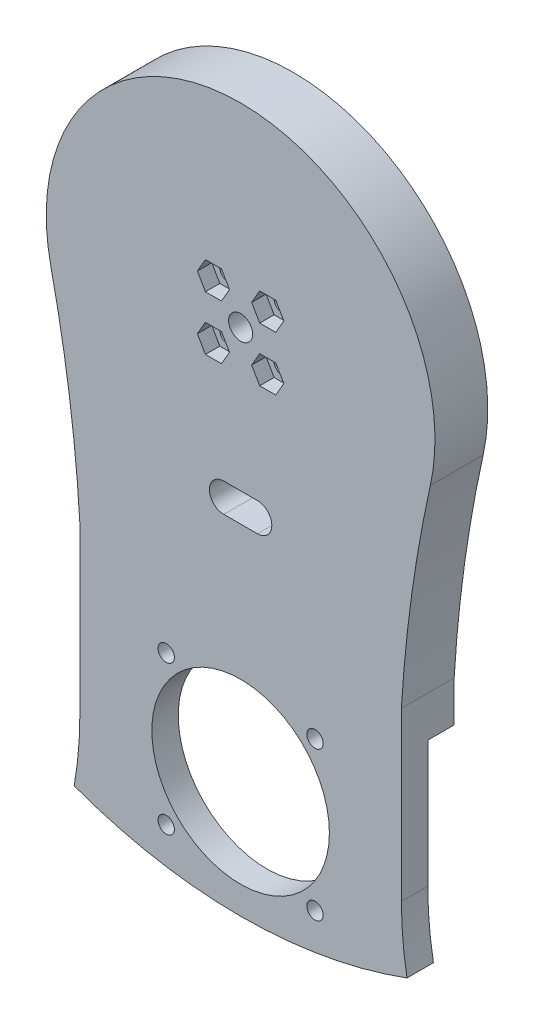
SolidWorks part; units mm, degrees
ref_plane "Front Plane" through (0, 0, 0) normal (0, 0, 1) x (1, 0, 0)
ref_plane "Top Plane" through (0, 0, 0) normal (0, 1, 0) x (1, 0, 0)
ref_plane "Right Plane" through (0, 0, 0) normal (1, 0, 0) x (0, 0, -1)
sketch "Sketch1" plane through (0, 0, 0) normal (0, 0, 1) x (1, 0, 0)
  line L0 (-79.9282, -98) -> (79.9282, -98) construction
  line L1 (-21.5, 21.5) -> (21.5, 21.5)
  line L2 (-21.5, 21.5) -> (-21.5, -21.5)
  line L3 (-21.5, -21.5) -> (21.5, -21.5)
  line L4 (21.5, 21.5) -> (21.5, -21.5)
  line L5 (-21.5, 21.5) -> (21.5, -21.5) construction
  line L6 (-21.5, -21.5) -> (21.5, 21.5) construction
  line L7 (-33.5, 21.5) -> (33.5, 21.5)
  line L8 (-33.5, 21.5) -> (-33.5, -31.5)
  line L9 (-33.5, -31.5) -> (33.5, -31.5)
  line L10 (33.5, 21.5) -> (33.5, -31.5)
  line L11 (-33.5, 21.5) -> (33.5, -31.5) construction
  line L12 (-33.5, -31.5) -> (33.5, 21.5) construction
  line L13 (-59.5091, 0) -> (49.588, 0) construction
  line L14 (0, -98) -> (-73.46, -24.54) construction
  line L15 (0, -98) -> (0, 0) construction
  line L16 (0, -98) -> (73.46, -24.54) construction
  line L17 (-51.5944, -53.7053) -> (51.5944, -53.7053)
  line L18 (0, -98) -> (0, 62) construction
  line L19 (0, 62) -> (0, 86) construction
  line L20 (-33.5, -31.5) -> (-38.3942, -31.5)
  line L21 (33.5, -31.5) -> (38.3942, -31.5)
  line L22 (-33.5, -30) -> (33.5, -30)
  line L23 (33.5, -30) -> (37.8422, -30)
  line L24 (-33.5, -30) -> (-37.8422, -30)
  circle A2 centre (-33.5, 0) radius 2.5982 construction
  circle A3 centre (-48.0833, -49.9167) radius 10.7942 construction
  circle A4 centre (48.0833, -49.9167) radius 10.7942 construction
  circle A5 centre (33.5, 0) radius 2.5982 construction
  arc A6 (-51.5944, -53.7053) -> (-33.5, -4.8509) centre (-108.5, -4.8509) ccw
  circle A7 centre (0, -98) radius 34.0704
  circle A8 centre (0, -98) radius 68
  arc A9 (51.5944, -53.7053) -> (33.5, -4.8509) centre (108.5, -4.8509) cw
  circle A10 centre (0, 0) radius 18.5
  point P0 (0, 0)
  point P6 (0, -5)
  point P38 (0, -98)
  dimension "D6" = 136
  dimension "D7" = 68.1408
  dimension "D10" = 75
  dimension "D11" = 75
  dimension "D13" = 37
  dimension "D1" = 43
  dimension "D2" = 43
  dimension "D3" = 53
  dimension "D4" = 10
  dimension "D5" = 12
  dimension "D8" = 26.3509
  dimension "D9" = 26.3509
  dimension "D12" = 103.1888
  dimension "D14" = 18.4167
  dimension "D15" = 14.5833
  dimension "D16" = 14.5833
  dimension "D17" = 18.4167
  dimension "D18" = 22.2053
  dimension "D19" = 159.8564
  dimension "D20" = 103.8881
  dimension "D21" = 103.8881
  dimension "D22" = 160
  dimension "D23" = 62
  dimension "D24" = 184
extrude "Boss-Extrude1" add sketch "Sketch1" along normal blind 5.5 contours A6 L24 L8 | L8 L22 L10 L7 L4 L3 L2 | L23 A9 L10 | L4 L1 L2 L3 A10 | A8 A9 L21 L9 | A8 L9 L20 A6 | A8 L22 L8 L9 | A8 L9 L10 L22 | L21 A9 L23 L10 | A6 L20 L8 L24 region at (0, 20.8919, 0) region at (-22.3451, 0, 0) region at (-34.7959, -23.7497, 0) region at (34.7959, -23.7497, 0) region at (-21.2623, -30.6909, 0) region at (-35.8103, -30.7649, 0) region at (35.8103, -30.7649, 0) region at (21.2623, -30.6909, 0) region at (-34.2049, -36.6082, 0) region at (34.2049, -36.6082, 0)
sketch "Sketch2" plane through (0, 0, 5.5) normal (0, 0, 1) x (1, 0, 0)
  line L0 (0, 0) -> (0, 82) construction
  line L1 (-33.5, 21.5) -> (33.5, 21.5)
  line L2 (33.5, 21.5) -> (33.5, 30)
  line L3 (33.5, 30) -> (-33.5, 30)
  line L4 (-33.5, 21.5) -> (-33.5, 30)
  line L5 (-8, 82) -> (8, 82) construction
  line L6 (-5.6569, 87.6569) -> (0, 82)
  line L7 (-5.6569, 76.3431) -> (0, 82) construction
  line L8 (0, 82) -> (5.6569, 87.6569) construction
  line L9 (0, 82) -> (5.6569, 76.3431) construction
  circle A0 centre (0, 0) radius 18.5 construction
  circle A1 centre (0, -98) radius 68 construction
  circle A2 centre (0, 82) radius 2.5
  circle A3 centre (0, 82) radius 8 construction
  circle A4 centre (0, 82) radius 40.5
  circle A5 centre (0, 0) radius 27.5 construction
  arc A6 (-33.5, 30) -> (-39.5426, 73.2458) centre (-309.506, 13.4799) ccw
  circle A7 centre (0, 82) radius 40 construction
  arc A8 (33.5, 30) -> (39.5426, 73.2458) centre (309.506, 13.4799) cw
  circle A14 centre (-5.6569, 87.6569) radius 1.7
  circle A15 centre (5.6569, 87.6569) radius 1.7
  circle A16 centre (5.6569, 76.3431) radius 1.7
  circle A17 centre (-5.6569, 76.3431) radius 1.7
  line M4 (33.5, 21.5) -> (-33.5, 21.5)
  dimension "D3" = 136
  dimension "D4" = 37
  dimension "D5" = 5
  dimension "D6" = 16
  dimension "D7" = 81
  dimension "D8" = 55
  dimension "D9" = 30
  dimension "D10" = 80
  dimension "D11" = 553
  dimension "D12" = 276.5
  dimension "D13" = 45
  dimension "D14" = 3.4
  dimension "D15" = 3.4
  dimension "D16" = 3.4
  dimension "D17" = 3.4
  dimension "D1" = 98
  dimension "D2" = 180
  dimension "D18" = 45
  dimension "D19" = 45
  dimension "D20" = 45
extrude "Boss-Extrude2" add sketch "Sketch2" against normal blind 11 contours L3 A8 A4 A6 | L4 L2 L3 M4 | A4 A2 region at (0, 25.75, 5.5) region at (0, 40.4579, 5.5) region at (-4.2786, 121.1212, 5.5)
sketch "Sketch3" plane through (0, 0, 5.5) normal (0, 0, 1) x (1, 0, 0)
  line L1 (-15.5, -15.5) -> (15.5, -15.5) construction
  line L2 (-15.5, -15.5) -> (-15.5, 15.5) construction
  line L3 (-15.5, 15.5) -> (15.5, 15.5) construction
  line L4 (15.5, -15.5) -> (15.5, 15.5) construction
  line L5 (-15.5, -15.5) -> (15.5, 15.5) construction
  line L6 (-15.5, 15.5) -> (15.5, -15.5) construction
  circle A0 centre (-15.5, 15.5) radius 1.7
  circle A1 centre (15.5, 15.5) radius 1.7
  circle A2 centre (15.5, -15.5) radius 1.7
  circle A3 centre (-15.5, -15.5) radius 1.7
  point P0 (0, 0)
  point P16 (0, 0)
  dimension "D3" = 3.4
  dimension "D1" = 31
  dimension "D2" = 31
  dimension "D4" = 4
extrude "Cut-Extrude1" cut sketch "Sketch3" against normal through all contours A3 | A2 | A1 | A0
sketch "Sketch4" plane through (0, 0, 0) normal (0, 0, -1) x (-1, 0, 0)
  line L0 (-33.5, 21.5) -> (33.5, 21.5) construction
  line L1 (-33.5, 21.5) -> (-33.5, -18.5) construction
  line L2 (33.5, 21.5) -> (33.5, -18.5) construction
  line L3 (-33.5, -18.5) -> (33.5, -18.5) construction
  line L4 (-33.5, -18.5) -> (33.5, -18.5)
  line L5 (-65, -0.2716) -> (-65, -64.2716)
  line L6 (-65, -64.2716) -> (65, -64.2716)
  line L7 (65, -0.2716) -> (65, -64.2716)
  circle A0 centre (0, 0) radius 18.5
  arc A1 (-65, -0.2716) -> (65, -0.2716) centre (0, 75.7218) ccw
  arc M14 (51.5944, -53.7053) -> (33.5, -4.8509) centre (108.5, -4.8509) cw
  arc M18 (-33.5, -4.8509) -> (-51.5944, -53.7053) centre (-108.5, -4.8509) cw
  arc M19 (-51.5944, -53.7053) -> (51.5944, -53.7053) centre (0, -98) cw
  dimension "D2" = 200
  dimension "D3" = 100
  dimension "D6" = 37
  dimension "D1" = 40
  dimension "D4" = 64
  dimension "D5" = 130
  dimension "D7" = 64
extrude "Cut-Extrude11" cut sketch "Sketch4" against normal blind 10 contours A1 M18 M19 M14 region at (0, -29.6272, 0)
sketch "Sketch5" plane through (0, 0, 5.5) normal (0, 0, 1) x (1, 0, 0)
  line L0 (-7.3319, 90.558) -> (-3.9819, 84.7557) construction
  line L1 (-7.3319, 84.7557) -> (-3.9819, 90.558) construction
  line L2 (-9.0069, 87.6569) -> (-2.3069, 87.6569) construction
  line L3 (2.3069, 87.6569) -> (9.0069, 87.6569) construction
  line L4 (-9.0069, 76.3431) -> (-2.3069, 76.3431) construction
  line L5 (2.3069, 76.3431) -> (9.0069, 76.3431) construction
  line L6 (3.9819, 90.558) -> (7.3319, 84.7557) construction
  line L7 (3.9819, 84.7557) -> (7.3319, 90.558) construction
  line L8 (3.9819, 79.2443) -> (7.3319, 73.442) construction
  line L9 (3.9819, 73.442) -> (7.3319, 79.2443) construction
  line L10 (-7.3319, 79.2443) -> (-3.9819, 73.442) construction
  line L11 (-7.3319, 73.442) -> (-3.9819, 79.2443) construction
  line L12 (-7.3319, 90.558) -> (-3.9819, 90.558)
  line L13 (-3.9819, 90.558) -> (-2.3069, 87.6569)
  line L14 (-2.3069, 87.6569) -> (-3.9819, 84.7557)
  line L15 (-3.9819, 84.7557) -> (-7.3319, 84.7557)
  line L16 (-7.3319, 84.7557) -> (-9.0069, 87.6569)
  line L17 (-9.0069, 87.6569) -> (-7.3319, 90.558)
  line L18 (3.9819, 90.558) -> (7.3319, 90.558)
  line L19 (7.3319, 90.558) -> (9.0069, 87.6569)
  line L20 (9.0069, 87.6569) -> (7.3319, 84.7557)
  line L21 (7.3319, 84.7557) -> (3.9819, 84.7557)
  line L22 (3.9819, 84.7557) -> (2.3069, 87.6569)
  line L23 (2.3069, 87.6569) -> (3.9819, 90.558)
  line L24 (-7.3319, 79.2443) -> (-9.0069, 76.3431)
  line L25 (-9.0069, 76.3431) -> (-7.3319, 73.442)
  line L26 (-7.3319, 73.442) -> (-3.9819, 73.442)
  line L27 (-3.9819, 73.442) -> (-2.3069, 76.3431)
  line L28 (-2.3069, 76.3431) -> (-3.9819, 79.2443)
  line L29 (-3.9819, 79.2443) -> (-7.3319, 79.2443)
  line L30 (3.9819, 79.2443) -> (7.3319, 79.2443)
  line L31 (7.3319, 79.2443) -> (9.0069, 76.3431)
  line L32 (9.0069, 76.3431) -> (7.3319, 73.442)
  line L33 (7.3319, 73.442) -> (3.9819, 73.442)
  line L34 (3.9819, 73.442) -> (2.3069, 76.3431)
  line L35 (2.3069, 76.3431) -> (3.9819, 79.2443)
  circle A0 centre (-5.6569, 87.6569) radius 3.35 construction
  circle A1 centre (5.6569, 87.6569) radius 3.35 construction
  circle A2 centre (5.6569, 76.3431) radius 3.35 construction
  circle A3 centre (-5.6569, 76.3431) radius 3.35 construction
  dimension "D1" = 6.7
  dimension "D2" = 6.7
  dimension "D3" = 6.7
  dimension "D4" = 6.7
  dimension "D5" = 60
  dimension "D6" = 60
  dimension "D7" = 60
  dimension "D8" = 60
  dimension "D9" = 60
  dimension "D10" = 60
  dimension "D11" = 60
  dimension "D12" = 60
extrude "Cut-Extrude12" cut sketch "Sketch5" against normal blind 3
sketch "Sketch6" plane through (0, 0, -5.5) normal (0, 0, -1) x (-1, 0, 0)
  line L0 (3.5, 49.5) -> (-3.5, 49.5) construction
  line L1 (3.5, 46.5) -> (-3.5, 46.5)
  line L2 (3.5, 52.5) -> (-3.5, 52.5)
  line L3 (-33.5, 21.5) -> (33.5, 21.5) construction
  arc A0 (3.5, 46.5) -> (3.5, 52.5) centre (3.5, 49.5) ccw
  arc A1 (-3.5, 52.5) -> (-3.5, 46.5) centre (-3.5, 49.5) ccw
  point P2 (0, 49.5)
  dimension "D1" = 3
  dimension "D2" = 7
  dimension "D3" = 28
extrude "Cut-Extrude13" cut sketch "Sketch6" against normal through all
